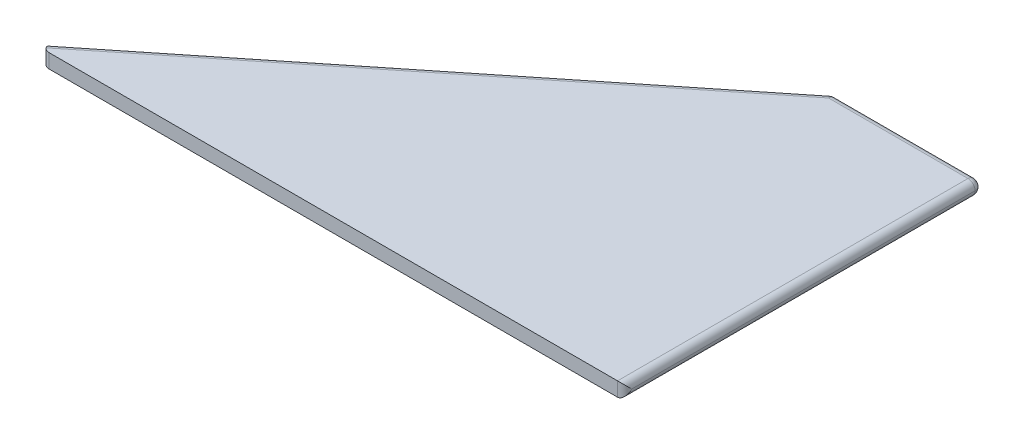
SolidWorks part; units mm, degrees
ref_plane "Front Plane" through (0, 0, 0) normal (0, 0, 1) x (1, 0, 0)
ref_plane "Top Plane" through (0, 0, 0) normal (0, 1, 0) x (1, 0, 0)
ref_plane "Right Plane" through (0, 0, 0) normal (1, 0, 0) x (0, 0, -1)
sketch "Sketch1" plane through (0, 0, 0) normal (0, 1, 0) x (1, 0, 0)
  line L0 (0, 0) -> (0, 120)
  line L1 (0, 120) -> (-50, 120)
  line L7 (0, 0) -> (-200, 0)
  line L8 (-50, 120) -> (-200, 0)
  dimension "D2" = 120
  dimension "D3" = 200
  dimension "D4" = 50
extrude "Boss-Extrude1" add sketch "Sketch1" along normal blind 4.76
fillet "Fillet3" radius 2.38 10 edges at (-125, 4.76, -60) (-200, 2.38, 0) (-125, 0, -60) (-25, 4.76, -120) (-50, 2.38, -120) (-25, 0, -120) (0, 2.38, 0) (0, 4.76, -60) (0, 2.38, -120) (0, 0, -60)
